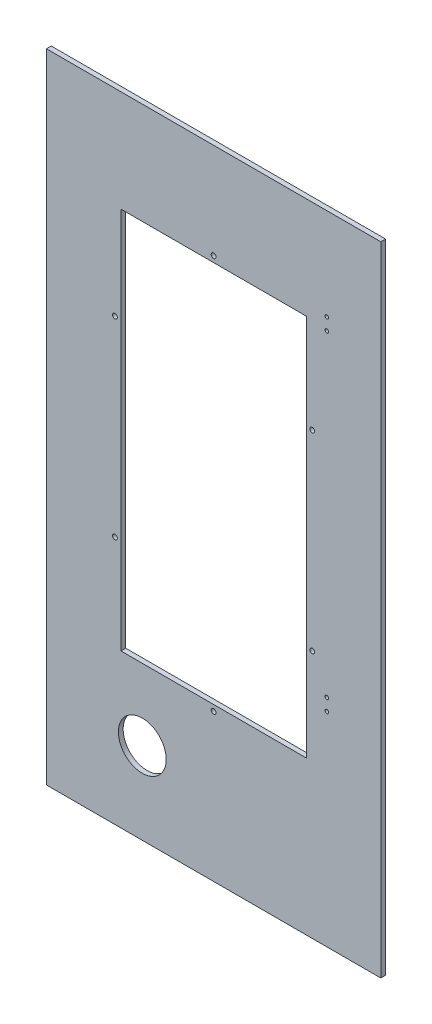
SolidWorks part; units mm, degrees
ref_plane "Спереди" through (0, 0, 0) normal (0, 0, 1) x (1, 0, 0)
ref_plane "Сверху" through (0, 0, 0) normal (0, 1, 0) x (1, 0, 0)
ref_plane "Справа" through (0, 0, 0) normal (1, 0, 0) x (0, 0, -1)
sketch "Эскиз1" plane through (0, 0, 0) normal (0, 1, 0) x (1, 0, 0)
  line L1 (-144.7882, -1.3414) -> (134.7883, -1.3414)
  line L2 (-144.7882, -1.3414) -> (-144.7882, -5.3414)
  line L3 (-144.7882, -5.3414) -> (134.7883, -5.3414)
  line L4 (134.7883, -1.3414) -> (134.7883, -5.3414)
  dimension "D1" = 4
extrude "Вытянуть1" add sketch "Эскиз1" along normal up to surface (533.2137 mm away)
sketch "Эскиз2" plane through (0, 0, 1.3414) normal (0, 0, -1) x (-1, 0, 0)
  circle A0 centre (64.6516, 68.5542) radius 20
extrude "Вырез-Вытянуть1" cut sketch "Эскиз2" against normal through all
sketch "Sketch1" plane through (0, 0, 1.3414) normal (0, 0, -1) x (-1, 0, 0)
  line L0 (-201.6101, 448.2137) -> (228.2599, 448.2137) construction
  line L3 (-351.4591, 128.2137) -> (303.9412, 128.2137) construction
  line L4 (-134.7883, 533.2137) -> (144.7882, 533.2137) construction
  line L5 (5, 533.2137) -> (5, 456.8501) construction
  line L6 (-238.6939, 288.2137) -> (-171.3376, 288.2137) construction
  line L9 (-72.5, 448.2137) -> (82.5, 448.2137)
  line L10 (-72.5, 448.2137) -> (-72.5, 128.2137)
  line L11 (-72.5, 128.2137) -> (82.5, 128.2137)
  line L12 (82.5, 448.2137) -> (82.5, 128.2137)
  line L13 (-72.5, 448.2137) -> (82.5, 128.2137) construction
  line L14 (-72.5, 128.2137) -> (82.5, 448.2137) construction
  point P9 (5, 288.2137)
  dimension "D1" = 320
  dimension "D2" = 85
  dimension "D3" = 160
extrude "Cut-Extrude1" cut sketch "Sketch1" against normal through all contours L10 L11 L12 L9
sketch "Sketch2" plane through (0, 0, 5.3414) normal (0, 0, 1) x (1, 0, 0)
  line L0 (-82.5, 448.2137) -> (-82.5, 128.2137) construction
  line L1 (72.5, 448.2137) -> (-82.5, 448.2137) construction
  line L2 (-82.5, 288.2137) -> (-125.5991, 288.2137) construction
  line L3 (-5, 127.0553) -> (-5, 276.1441) construction
  circle A0 centre (-87.5, 368.2137) radius 2
  circle A1 centre (-87.5, 208.2137) radius 2
  circle A2 centre (77.5, 208.2137) radius 2
  circle A3 centre (77.5, 368.2137) radius 2
  circle A4 centre (-5, 453.2137) radius 2
  circle A5 centre (-5, 123.2137) radius 2
  circle A6 centre (89.7398, 456.26) radius 1.5
  circle A7 centre (89.7398, 446.0875) radius 1.5
  circle A8 centre (89.7398, 180.6489) radius 1.5
  circle A9 centre (89.7398, 170.4764) radius 1.5
  dimension "D1" = 5
  dimension "D3" = 5
  dimension "D2" = 80
extrude "Cut-Extrude2" cut sketch "Sketch2" against normal through all
